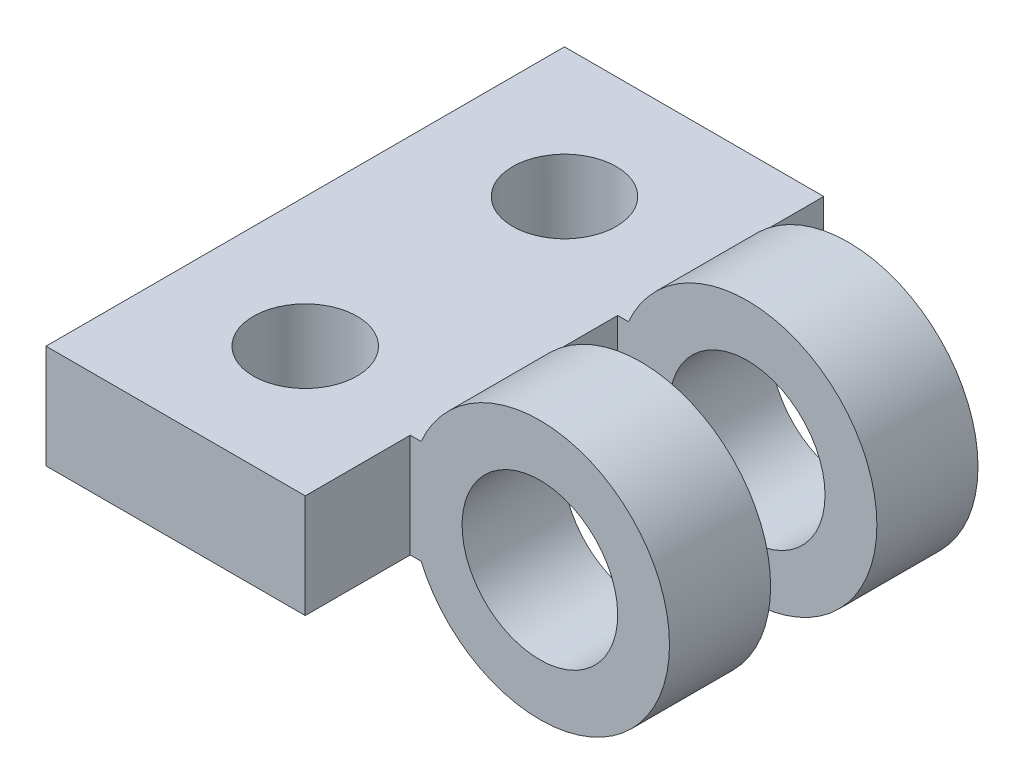
SolidWorks part; units mm, degrees
ref_plane "Front Plane" through (0, 0, 0) normal (0, 0, 1) x (1, 0, 0)
ref_plane "Top Plane" through (0, 0, 0) normal (0, 1, 0) x (1, 0, 0)
ref_plane "Right Plane" through (0, 0, 0) normal (1, 0, 0) x (0, 0, -1)
sketch "Sketch2" plane through (0, 0, 0) normal (0, 0, 1) x (1, 0, 0)
  circle A0 centre (0, 0) radius 2.5
  circle A1 centre (0, 0) radius 1.5
  dimension "D1" = 5
  dimension "D2" = 3
extrude "Boss-Extrude1" add sketch "Sketch2" along normal blind 1.95
sketch "Sketch3" plane through (0, 0, 0) normal (0, 1, 0) x (1, 0, 0)
  line L0 (-2.5, 0) -> (-2.5, -1.95) construction
  line L1 (-2.5, 2.025) -> (-7.5, 2.025)
  line L2 (-2.5, 2.025) -> (-2.5, -7.975)
  line L3 (-2.5, -7.975) -> (-7.5, -7.975)
  line L4 (-7.5, 2.025) -> (-7.5, -7.975)
  line L5 (0, 0) -> (0, -1.95) construction
  line L6 (-2.5, -1.95) -> (2.5, -1.95) construction
  line L7 (0, -0.975) -> (-2.5, -0.975) construction
  dimension "D1" = 10
  dimension "D2" = 5
  dimension "D3" = 0
  dimension "D4" = 3
extrude "Boss-Extrude2" add sketch "Sketch3" along normal blind 1 and the other way blind 1 separate body
sketch "Sketch4" plane through (-2.5, 0, 0) normal (1, 0, 0) x (0, 0, -1)
  line L0 (-4.975, 1) -> (-4.975, -1) construction
  line L1 (-7.975, 1) -> (2.025, 1) construction
  line L2 (-7.975, -1) -> (2.025, -1) construction
  line L3 (-7.975, -1) -> (-7.975, 1) construction
  dimension "D1" = 3
ref_plane "Plane1" through (0, 0, 4.975) normal (0, 0, 1) x (0, -1, 0)
sketch "Sketch5" plane through (0, 0, 4.975) normal (0, 0, 1) x (0, -1, 0)
  circle A0 centre (0, 0) radius 2.5
  circle A1 centre (0, 0) radius 1.5006
extrude "Boss-Extrude3" add sketch "Sketch5" along normal blind 0.975 and the other way blind 0.975 separate body
sketch "Sketch6" plane through (-2.5, 0, 0) normal (1, 0, 0) x (0, 0, -1)
  line L0 (-5.95, 2.5) -> (-5.95, -2.5) construction
  line L1 (-5.95, 1) -> (-4, 1)
  line L2 (-5.95, 1) -> (-5.95, -1)
  line L3 (-5.95, -1) -> (-4, -1)
  line L4 (-4, 1) -> (-4, -1)
  line L5 (-7.975, 1) -> (2.025, 1) construction
  line L6 (-4, -2.5) -> (-4, 2.5) construction
  line L7 (-7.975, -1) -> (2.025, -1) construction
  line L8 (-1.95, 2.5) -> (-1.95, -2.5) construction
  line L9 (-1.95, 1) -> (0, 1)
  line L10 (-1.95, 1) -> (-1.95, -1)
  line L11 (-1.95, -1) -> (0, -1)
  line L12 (0, 1) -> (0, -1)
  line L13 (0, -2.5) -> (0, 2.5) construction
extrude "Boss-Extrude4" add sketch "Sketch6" along normal up to surface (0.2087 mm away) up to face at (0, -2.5, 4)
sketch "Sketch7" plane through (0, 1, 0) normal (0, 1, 0) x (1, 0, 0)
  line L0 (-5, -2.975) -> (-5, -7.975) construction
  line L3 (-2.5, -2.975) -> (-7.5, -2.975) construction
  line L4 (-2.5, -4) -> (-2.5, -1.95) construction
  line L5 (-7.5, 2.025) -> (-7.5, -7.975) construction
  line L6 (-7.5, -7.975) -> (-2.5, -7.975) construction
  circle A0 centre (-5, -5.475) radius 1
  circle A1 centre (-5, -0.475) radius 1
  dimension "D1" = 2
extrude "Cut-Extrude1" cut sketch "Sketch7" against normal blind 10
